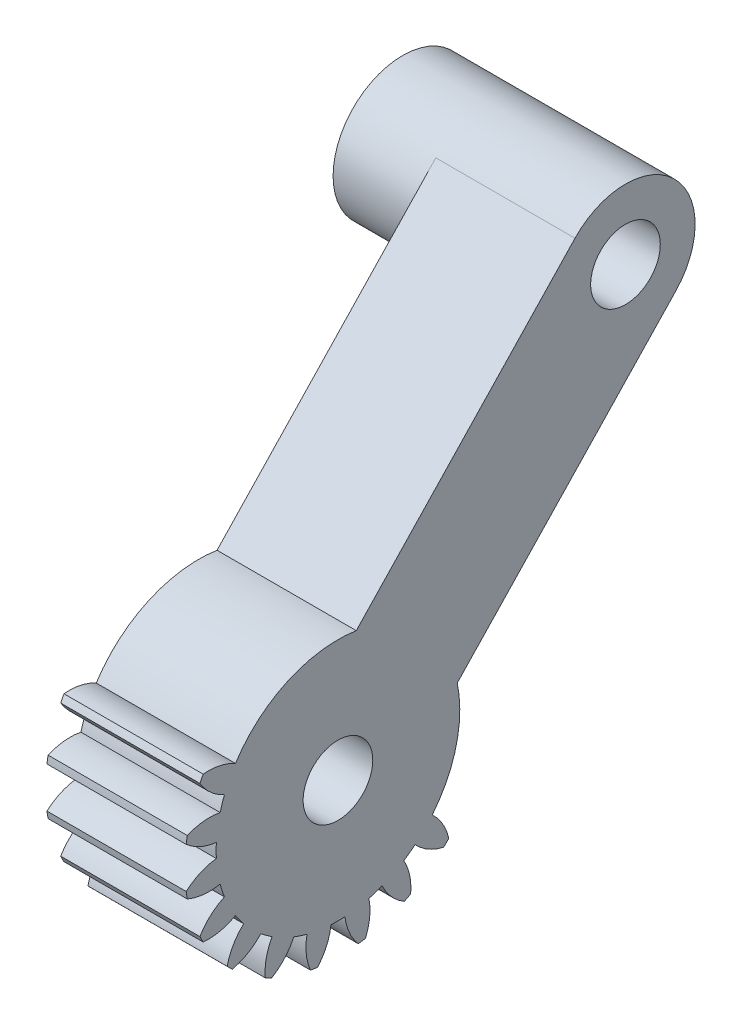
SolidWorks part; units mm, degrees
ref_plane "Front Plane" through (0, 0, 0) normal (0, 0, 1) x (1, 0, 0)
ref_plane "Top Plane" through (0, 0, 0) normal (0, 1, 0) x (1, 0, 0)
ref_plane "Right Plane" through (0, 0, 0) normal (1, 0, 0) x (0, 0, -1)
ref_plane "Plane1" through (4.0439, 0, 0) normal (1, 0, 0) x (0, 0, -1)
sketch "Sketch1" plane through (4.0439, 0, 0) normal (1, 0, 0) x (0, 0, -1)
  circle A0 centre (0.8725, -1.1221) radius 2.5
  arc A1 (-10.0295, 0.3429) -> (-7.8622, -0.6222) centre (-7.392, 3.3501) ccw
  arc A2 (-7.8622, -0.6222) -> (-7.8622, -1.622) centre (0.8725, -1.1221) ccw
  arc A3 (-7.8622, -1.622) -> (-10.0295, -2.587) centre (-7.392, -5.5943) ccw
  arc A4 (-10.0295, -2.587) -> (-9.9487, -3.0977) centre (0.8725, -1.1221) ccw
  arc A5 (-9.9487, -3.0977) -> (-7.5892, -3.3458) centre (-8.3695, 0.5774) ccw
  arc A6 (-7.5892, -3.3458) -> (-7.2802, -4.2967) centre (0.8725, -1.1221) ccw
  arc A7 (-7.2802, -4.2967) -> (-9.0433, -5.8842) centre (-5.6055, -7.9292) ccw
  arc A8 (-9.0433, -5.8842) -> (-8.8085, -6.3449) centre (0.8725, -1.1221) ccw
  arc A9 (-8.8085, -6.3449) -> (-6.4879, -5.8518) centre (-8.4423, -2.3617) ccw
  arc A10 (-6.4879, -5.8518) -> (-5.9002, -6.6607) centre (0.8725, -1.1221) ccw
  arc A11 (-5.9002, -6.6607) -> (-7.0864, -8.7153) centre (-3.185, -9.5979) ccw
  arc A12 (-7.0864, -8.7153) -> (-6.7207, -9.0809) centre (0.8725, -1.1221) ccw
  arc A13 (-6.7207, -9.0809) -> (-4.6661, -7.8948) centre (-7.6033, -5.1795) ccw
  arc A14 (-4.6661, -7.8948) -> (-3.8572, -8.4825) centre (0.8725, -1.1221) ccw
  arc A15 (-3.8572, -8.4825) -> (-4.3504, -10.8031) centre (-0.3672, -10.4369) ccw
  arc A16 (-4.3504, -10.8031) -> (-3.8897, -11.0378) centre (0.8725, -1.1221) ccw
  arc A17 (-3.8897, -11.0378) -> (-2.3022, -9.2748) centre (-5.9347, -7.6001) ccw
  arc A18 (-2.3022, -9.2748) -> (-1.3512, -9.5838) centre (0.8725, -1.1221) ccw
  arc A19 (-1.3512, -9.5838) -> (-1.1032, -11.9432) centre (2.5719, -10.3641) ccw
  arc A20 (-1.1032, -11.9432) -> (-0.5925, -12.0241) centre (0.8725, -1.1221) ccw
  arc A21 (-0.5925, -12.0241) -> (0.3725, -9.8568) centre (-3.5997, -9.3866) ccw
  arc A22 (0.3725, -9.8568) -> (1.3724, -9.8568) centre (0.8725, -1.1221) ccw
  arc A23 (1.3724, -9.8568) -> (2.3374, -12.0241) centre (5.3447, -9.3866) ccw
  arc A24 (2.3374, -12.0241) -> (2.8481, -11.9432) centre (0.8725, -1.1221) ccw
  arc A25 (2.8481, -11.9432) -> (3.0962, -9.5838) centre (-0.827, -10.3641) ccw
  arc A26 (3.0962, -9.5838) -> (4.0471, -9.2748) centre (0.8725, -1.1221) ccw
  arc A27 (4.0471, -9.2748) -> (5.6346, -11.0378) centre (7.6796, -7.6001) ccw
  arc A28 (5.6346, -11.0378) -> (6.0953, -10.8031) centre (0.8725, -1.1221) ccw
  arc A29 (6.0953, -10.8031) -> (5.6022, -8.4825) centre (2.1121, -10.4369) ccw
  arc A30 (5.6022, -8.4825) -> (6.411, -7.8948) centre (0.8725, -1.1221) ccw
  arc A31 (6.411, -7.8948) -> (8.4657, -9.0809) centre (9.3483, -5.1795) ccw
  arc A32 (8.4657, -9.0809) -> (8.8313, -8.7153) centre (0.8725, -1.1221) ccw
  arc A33 (8.8313, -8.7153) -> (7.6451, -6.6607) centre (4.9299, -9.5979) ccw
  arc A34 (7.6451, -6.6607) -> (8.2328, -5.8518) centre (0.8725, -1.1221) ccw
  arc A35 (8.2328, -5.8518) -> (10.5535, -6.3449) centre (10.1873, -2.3617) ccw
  arc A36 (10.5535, -6.3449) -> (10.7882, -5.8842) centre (0.8725, -1.1221) ccw
  arc A37 (10.7882, -5.8842) -> (9.0252, -4.2967) centre (7.3505, -7.9292) ccw
  arc A38 (9.0252, -4.2967) -> (9.3342, -3.3458) centre (0.8725, -1.1221) ccw
  arc A39 (9.3342, -3.3458) -> (11.6936, -3.0977) centre (10.1144, 0.5774) ccw
  arc A40 (11.6936, -3.0977) -> (11.7745, -2.587) centre (0.8725, -1.1221) ccw
  arc A41 (11.7745, -2.587) -> (9.6072, -1.622) centre (9.137, -5.5943) ccw
  arc A42 (9.6072, -1.622) -> (9.6072, -0.6222) centre (0.8725, -1.1221) ccw
  arc A43 (9.6072, -0.6222) -> (11.7745, 0.3429) centre (9.137, 3.3501) ccw
  arc A44 (11.7745, 0.3429) -> (11.6936, 0.8536) centre (0.8725, -1.1221) ccw
  arc A45 (11.6936, 0.8536) -> (9.3342, 1.1016) centre (10.1144, -2.8215) ccw
  arc A46 (9.3342, 1.1016) -> (9.0252, 2.0526) centre (0.8725, -1.1221) ccw
  arc A47 (9.0252, 2.0526) -> (10.7882, 3.6401) centre (7.3505, 5.6851) ccw
  arc A48 (10.7882, 3.6401) -> (10.5535, 4.1008) centre (0.8725, -1.1221) ccw
  arc A49 (10.5535, 4.1008) -> (8.2328, 3.6076) centre (10.1873, 0.1176) ccw
  arc A50 (8.2328, 3.6076) -> (7.6451, 4.4165) centre (0.8725, -1.1221) ccw
  arc A51 (7.6451, 4.4165) -> (8.8313, 6.4711) centre (4.9299, 7.3537) ccw
  arc A52 (8.8313, 6.4711) -> (8.4657, 6.8368) centre (0.8725, -1.1221) ccw
  arc A53 (8.4657, 6.8368) -> (6.411, 5.6506) centre (9.3483, 2.9353) ccw
  arc A54 (6.411, 5.6506) -> (5.6022, 6.2383) centre (0.8725, -1.1221) ccw
  arc A55 (5.6022, 6.2383) -> (6.0953, 8.5589) centre (2.1121, 8.1927) ccw
  arc A56 (6.0953, 8.5589) -> (5.6346, 8.7937) centre (0.8725, -1.1221) ccw
  arc A57 (5.6346, 8.7937) -> (4.0471, 7.0306) centre (7.6796, 5.3559) ccw
  arc A58 (4.0471, 7.0306) -> (3.0962, 7.3396) centre (0.8725, -1.1221) ccw
  arc A59 (3.0962, 7.3396) -> (2.8481, 9.6991) centre (-0.827, 8.1199) ccw
  arc A60 (2.8481, 9.6991) -> (2.3374, 9.7799) centre (0.8725, -1.1221) ccw
  arc A61 (2.3374, 9.7799) -> (1.3724, 7.6126) centre (5.3447, 7.1424) ccw
  arc A62 (1.3724, 7.6126) -> (0.3725, 7.6126) centre (0.8725, -1.1221) ccw
  arc A63 (0.3725, 7.6126) -> (-0.5925, 9.7799) centre (-3.5997, 7.1424) ccw
  arc A64 (-0.5925, 9.7799) -> (-1.1032, 9.6991) centre (0.8725, -1.1221) ccw
  arc A65 (-1.1032, 9.6991) -> (-1.3512, 7.3396) centre (2.5719, 8.1199) ccw
  arc A66 (-1.3512, 7.3396) -> (-2.3022, 7.0306) centre (0.8725, -1.1221) ccw
  arc A67 (-2.3022, 7.0306) -> (-3.8897, 8.7937) centre (-5.9347, 5.3559) ccw
  arc A68 (-3.8897, 8.7937) -> (-4.3504, 8.5589) centre (0.8725, -1.1221) ccw
  arc A69 (-4.3504, 8.5589) -> (-3.8572, 6.2383) centre (-0.3672, 8.1927) ccw
  arc A70 (-3.8572, 6.2383) -> (-4.6661, 5.6506) centre (0.8725, -1.1221) ccw
  arc A71 (-4.6661, 5.6506) -> (-6.7207, 6.8368) centre (-7.6033, 2.9353) ccw
  arc A72 (-6.7207, 6.8368) -> (-7.0864, 6.4711) centre (0.8725, -1.1221) ccw
  arc A73 (-7.0864, 6.4711) -> (-5.9002, 4.4165) centre (-3.185, 7.3537) ccw
  arc A74 (-5.9002, 4.4165) -> (-6.4879, 3.6076) centre (0.8725, -1.1221) ccw
  arc A75 (-6.4879, 3.6076) -> (-8.8085, 4.1008) centre (-8.4423, 0.1176) ccw
  arc A76 (-8.8085, 4.1008) -> (-9.0433, 3.6401) centre (0.8725, -1.1221) ccw
  arc A77 (-9.0433, 3.6401) -> (-7.2802, 2.0526) centre (-5.6055, 5.6851) ccw
  arc A78 (-7.2802, 2.0526) -> (-7.5892, 1.1016) centre (0.8725, -1.1221) ccw
  arc A79 (-7.5892, 1.1016) -> (-9.9487, 0.8536) centre (-8.3695, -2.8215) ccw
  arc A80 (-9.9487, 0.8536) -> (-10.0295, 0.3429) centre (0.8725, -1.1221) ccw
extrude "Boss-Extrude1" add sketch "Sketch1" against normal blind 10
sketch "Sketch2" plane through (4.0439, 0, 0) normal (1, 0, 0) x (0, 0, -1)
  line L0 (0.8725, -1.1221) -> (21.5231, 20.6392) construction
  line L1 (-2.7544, 2.3197) -> (17.8962, 24.0809)
  line L2 (4.4993, -4.5639) -> (25.15, 17.1974)
  line L3 (0.8725, 18.0125) -> (0.8725, -1.1221) construction
  arc A0 (-2.7544, 2.3197) -> (4.4993, -4.5639) centre (0.8725, -1.1221) ccw
  arc A1 (25.15, 17.1974) -> (17.8962, 24.0809) centre (21.5231, 20.6392) ccw
  arc A2 (25.1179, 24.1144) -> (24.8055, 24.4109) centre (21.5231, 20.6392) ccw
  circle A3 centre (21.5231, 20.6392) radius 2.5
  point P3 (11.1978, 9.7585)
  dimension "D2" = 5
  dimension "D1" = 10
  dimension "D3" = 30
  dimension "D4" = 43.5
extrude "Boss-Extrude2" add sketch "Sketch2" against normal blind 10 contours L2 A1 L1 A0 A3 region at (4.0439, 9.1633, -10.6329)
sketch "Sketch3" plane through (-5.9561, 0, 0) normal (-1, 0, 0) x (0, 0, 1)
  circle A0 centre (-21.5231, 20.6392) radius 2.5
  circle A1 centre (-21.5231, 20.6392) radius 5
extrude "Boss-Extrude3" add sketch "Sketch3" along normal blind 6
sketch "Sketch4" plane through (4.0439, 0, 0) normal (1, 0, 0) x (0, 0, -1)
  circle A1 centre (0.8725, -1.1221) radius 2.5
  dimension "D1" = 5
extrude "Cut-Extrude1" cut sketch "Sketch4" against normal through all
sketch "Sketch5" plane through (4.0439, 0, 0) normal (1, 0, 0) x (0, 0, -1)
  circle A0 centre (0.8725, -1.1221) radius 9.5546
sketch "Sketch6" plane through (4.0439, 0, 0) normal (1, 0, 0) x (0, 0, -1)
  line L0 (4.5797, 10.0482) -> (2.1876, 7.5275)
  line L2 (11.8334, 3.1647) -> (9.4414, 0.644)
  line L4 (7.9481, -6.2679) -> (10.3909, -8.0444)
  line L5 (-6.161, 4.0813) -> (-8.5892, 5.8777)
  arc A0 (2.1876, 7.5275) -> (-6.161, 4.0813) centre (0.8725, -1.1221) ccw
  arc A1 (4.5797, 10.0482) -> (-8.5892, 5.8777) centre (0.8725, -1.1221) ccw
  arc A2 (7.9481, -6.2679) -> (9.4414, 0.644) centre (0.8725, -1.1221) ccw
  arc A3 (10.3909, -8.0444) -> (11.8334, 3.1647) centre (0.8725, -1.1221) ccw
extrude "Cut-Extrude2" cut sketch "Sketch6" against normal through all
